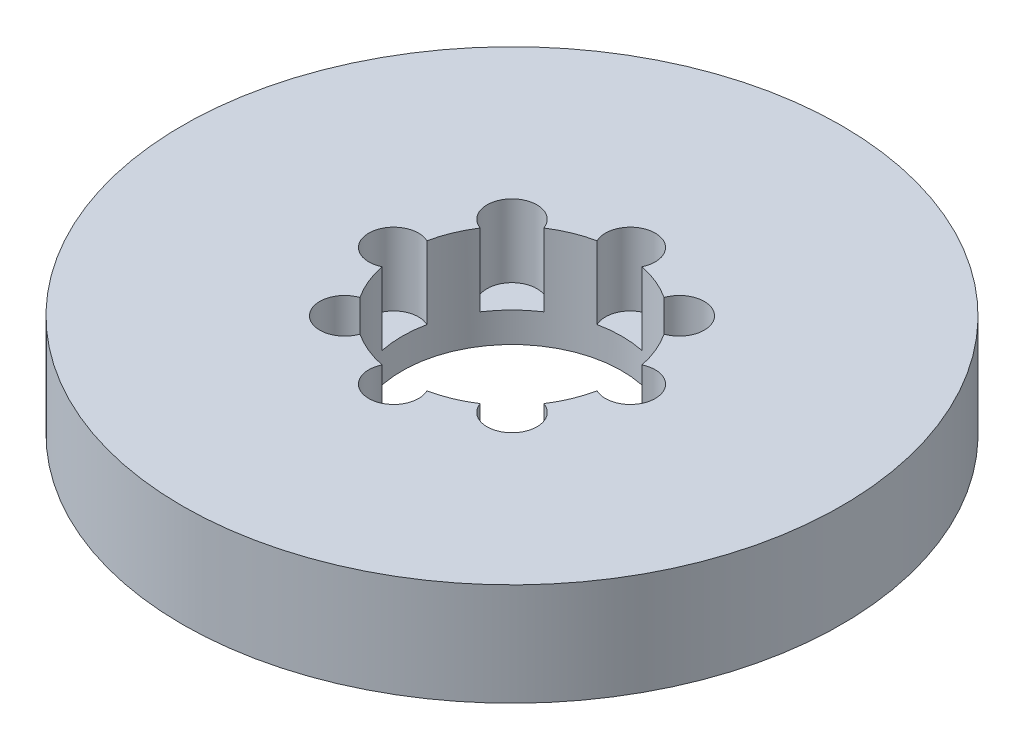
SolidWorks part; units mm, degrees
ref_plane "Front Plane" through (0, 0, 0) normal (0, 0, 1) x (1, 0, 0)
ref_plane "Top Plane" through (0, 0, 0) normal (0, 1, 0) x (1, 0, 0)
ref_plane "Right Plane" through (0, 0, 0) normal (1, 0, 0) x (0, 0, -1)
sketch "Sketch1" plane through (0, 0, 0) normal (0, 1, 0) x (1, 0, 0)
  circle A0 centre (0, 0) radius 90
  dimension "FLANGE_OD" = 180
extrude "Boss-Extrude1" add sketch "Sketch1" along normal blind 28
sketch "Sketch2" plane through (0, 0, 0) normal (0, 1, 0) x (1, 0, 0)
  circle A0 centre (0, 0) radius 30
  dimension "BORE_D" = 60
extrude "Cut-Extrude1" cut sketch "Sketch2" along normal through all
sketch "Sketch3" plane through (0, 28, 0) normal (0, 1, 0) x (1, 0, 0)
  circle A0 centre (0, 0) radius 32.3128 construction
  circle A1 centre (-32.3128, 0) radius 6.8091
  dimension "BOLT_D" = 13.6183
  dimension "BOLT_PCD" = 64.6257
extrude "Cut-Extrude2" cut sketch "Sketch3" against normal blind 19.8255
pattern_circular "CirPattern1" count 8 over 360 about axis through (0, 0, 0) along (0, 1, 0) of "Cut-Extrude2"
